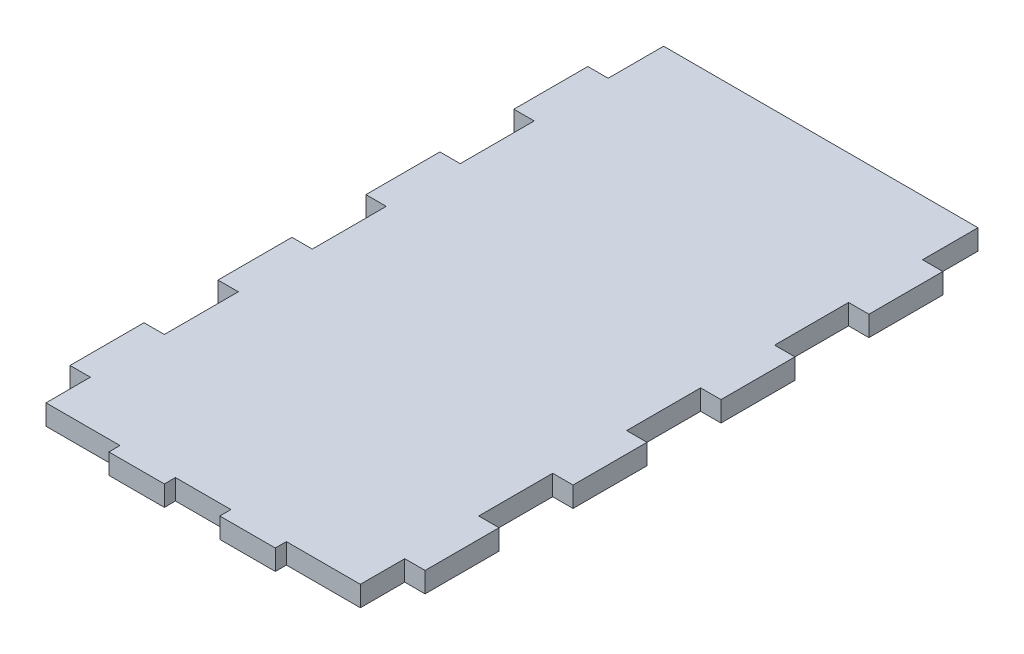
SolidWorks part; units mm, degrees
ref_plane "Alzado" through (0, 0, 0) normal (0, 0, 1) x (1, 0, 0)
ref_plane "Planta" through (0, 0, 0) normal (0, 1, 0) x (1, 0, 0)
ref_plane "Vista lateral" through (0, 0, 0) normal (1, 0, 0) x (0, 0, -1)
sketch "Croquis1" plane through (0, 0, 0) normal (0, 1, 0) x (1, 0, 0)
  line L0 (25.5, -2) -> (40.5, -2)
  line L1 (96, 13) -> (96, 33)
  line L2 (90.5, 168) -> (5.5, 168)
  line L3 (0, 153) -> (0, 93)
  line L5 (5.5, 73) -> (5.5, 93)
  line L6 (5.5, 93) -> (0, 93)
  line L7 (0, 93) -> (0, 113)
  line L8 (0, 113) -> (5.5, 113)
  line L9 (5.5, 113) -> (5.5, 133)
  line L10 (5.5, 133) -> (0, 133)
  line L11 (0, 133) -> (0, 153)
  line L12 (0, 153) -> (5.5, 153)
  line L13 (0, 13) -> (5.5, 13)
  line L14 (5.5, 33) -> (0, 33)
  line L15 (5.5, 53) -> (5.5, 33)
  line L16 (0, 53) -> (5.5, 53)
  line L17 (5.5, 73) -> (0, 73)
  line L18 (5.5, 153) -> (5.5, 168)
  line L19 (5.5, 13) -> (5.5, 1)
  line L20 (0, 33) -> (0, 13)
  line L21 (55.5, 1) -> (40.5, 1)
  line L22 (40.5, 1) -> (40.5, -2)
  line L23 (40.5, -2) -> (25.5, -2)
  line L24 (25.5, -2) -> (25.5, 1)
  line L25 (25.5, 1) -> (5.5, 1)
  line L26 (70.5, 1) -> (90.5, 1)
  line L27 (70.5, -2) -> (70.5, 1)
  line L28 (55.5, 1) -> (55.5, -2)
  line L29 (90.5, 13) -> (90.5, 1)
  line L30 (90.5, 153) -> (90.5, 168)
  line L31 (90.5, 73) -> (96, 73)
  line L32 (96, 53) -> (90.5, 53)
  line L33 (90.5, 53) -> (90.5, 33)
  line L34 (90.5, 33) -> (96, 33)
  line L35 (96, 13) -> (90.5, 13)
  line L36 (96, 153) -> (90.5, 153)
  line L37 (90.5, 133) -> (96, 133)
  line L38 (90.5, 113) -> (90.5, 133)
  line L39 (96, 113) -> (90.5, 113)
  line L40 (90.5, 93) -> (96, 93)
  line L41 (90.5, 73) -> (90.5, 93)
  line L42 (96, 133) -> (96, 153)
  line L43 (55.5, -2) -> (70.5, -2)
  line L44 (96, 53) -> (96, 73)
  line L45 (96, 93) -> (96, 113)
  line L46 (0, 73) -> (0, 53)
  dimension "D4" = 85
  dimension "D2" = 15
  dimension "D3" = 15
  dimension "D5" = 20
  dimension "D6" = 20
  dimension "D7" = 20
  dimension "D8" = 12
  dimension "D9" = 12
  dimension "D10" = 15
  dimension "D11" = 20
  dimension "D12" = 20
extrude "Saliente-Extruir1" add sketch "Croquis1" along normal blind 5.5 contours L17 L46 L16 L15 L14 L20 L13 L19 L25 L24 L0 L22 L21 L28 L43 L27 L26 L29 L35 L1 L34 L33 L32 L44 L31 L41 L40 L45 L39 L38 L37 L42 L36 L30 L2 L18 L12 L3 L10 L9 L8 L6 L5 region at (48, 0, -83.9085)
